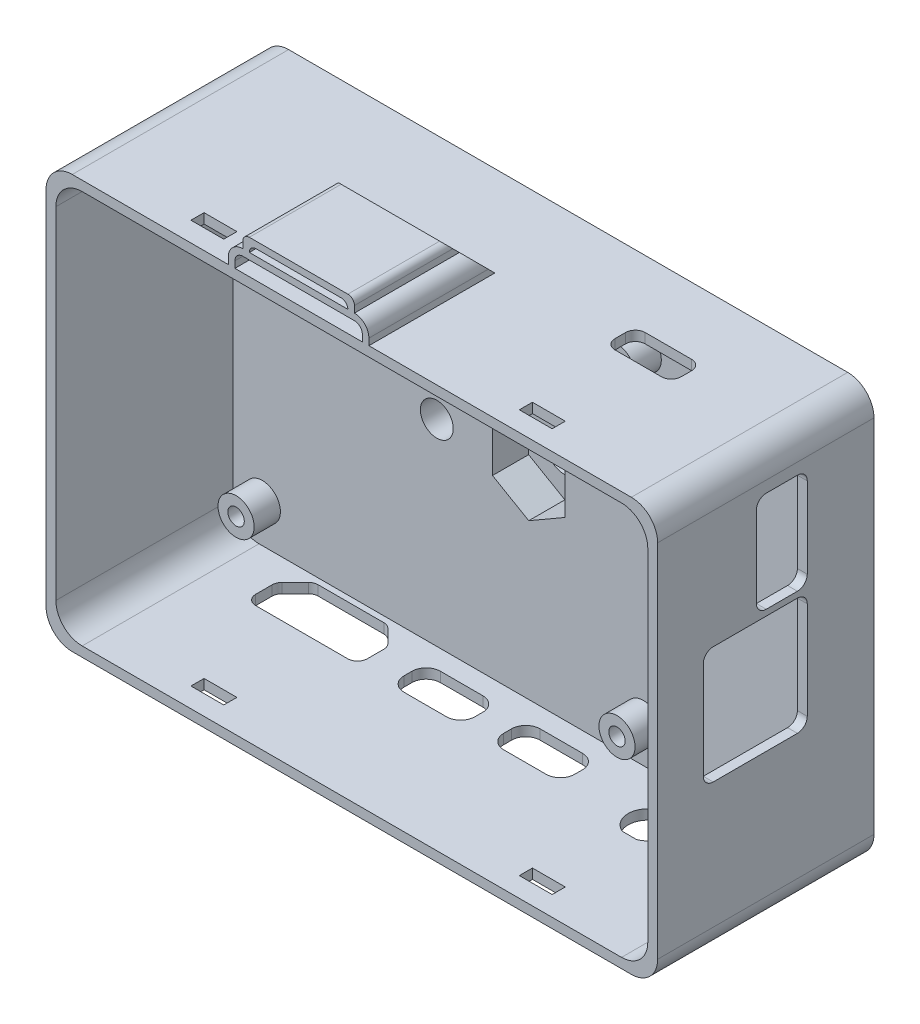
SolidWorks part; units mm, degrees
note: The reader was unsure of these and kept them because the rebuilt part matched: shared geometry of "Sketch1<3>", "Sketch8<2>".
ref_plane "Front Plane" through (0, 0, 0) normal (0, 0, 1) x (1, 0, 0)
ref_plane "Top Plane" through (0, 0, 0) normal (0, 1, 0) x (1, 0, 0)
ref_plane "Right Plane" through (0, 0, 0) normal (1, 0, 0) x (0, 0, -1)
sketch "Sketch1" plane through (0, 0, 0) normal (0, 0, 1) x (1, 0, 0)
  line L0 (46.565, -31.46) -> (46.565, 31.46)
  line L1 (45.065, -29.96) -> (-45.065, -29.96)
  line L2 (45.065, -29.96) -> (45.065, 29.96)
  line L3 (45.065, 29.96) -> (-45.065, 29.96)
  line L4 (-45.065, -29.96) -> (-45.065, 29.96)
  line L5 (45.065, -29.96) -> (-45.065, 29.96) construction
  line L6 (45.065, 29.96) -> (-45.065, -29.96) construction
  line L7 (46.565, 31.46) -> (-46.565, 31.46)
  line L8 (-46.565, -31.46) -> (-46.565, 31.46)
  line L9 (46.565, -31.46) -> (-46.565, -31.46)
  line L10 (44.065, 8.02) -> (44.065, -6.81) construction
  line L12 (21.895, 29.71) -> (28.965, 29.71) construction
  point P0 (0, 0)
  dimension "D2" = 1
  dimension "D3" = 0.25
  dimension "D1" = 1.5
extrude "Boss-Extrude1" add sketch "Sketch1" along normal blind 6 contours L2 L1 L4 L3
sketch "Sketch5" plane through (0, 0, 6) normal (0, 0, 1) x (1, 0, 0)
  circle A0 centre (17.435, -24.11) radius 1.4 construction
  circle A1 centre (-40.565, -24.11) radius 1.4 construction
  circle A2 centre (17.435, 24.89) radius 1.4 construction
  circle A3 centre (-40.565, 24.89) radius 1.4 construction
  circle A4 centre (17.435, -24.11) radius 1.4 construction
  circle A5 centre (-40.565, -24.11) radius 1.4 construction
  circle A6 centre (17.435, 24.89) radius 1.4 construction
  circle A7 centre (-40.565, 24.89) radius 1.4 construction
  circle A8 centre (17.435, 24.89) radius 1.25
  circle A9 centre (-40.565, 24.89) radius 1.25
  circle A10 centre (17.435, -24.11) radius 1.25
  circle A11 centre (-40.565, -24.11) radius 1.25
  circle A13 centre (-40.565, 24.89) radius 2.75
  circle A14 centre (17.435, 24.89) radius 2.75
  circle A15 centre (17.435, -24.11) radius 2.75
  circle A16 centre (-40.565, -24.11) radius 2.75
  dimension "D1" = 2.5
  dimension "D2" = 2.5
  dimension "D3" = 2.5
  dimension "D4" = 2.5
  dimension "D5" = 1.5
extrude "Boss-Extrude3" add sketch "Sketch5" along normal blind 4
extrude "Boss-Extrude2" add sketch "Sketch1<3>" along normal offset from surface (32.94 mm away) 6
sketch "Sketch1<3>" plane through (0, 0, 0) normal (0, 0, 1) x (1, 0, 0) same geometry as "Sketch1"
sketch "Sketch3" plane through (0, -31.46, 0) normal (0, -1, 0) x (1, 0, 0)
  line L31 (-19.165, 14.41) -> (-33.165, 14.41)
  line L32 (-34.665, 12.91) -> (-34.665, 10.4071)
  line L33 (-34.2257, 9.3464) -> (-32.2186, 7.3393)
  line L34 (-31.1579, 6.9) -> (-21.1721, 6.9)
  line L35 (-20.1114, 7.3393) -> (-18.1043, 9.3464)
  line L36 (-17.665, 10.4071) -> (-17.665, 12.91)
  line L37 (-19.165, 14.41) -> (-33.165, 14.41)
  line L38 (-34.665, 12.91) -> (-34.665, 10.4071)
  line L39 (-34.2257, 9.3464) -> (-32.2186, 7.3393)
  line L40 (-31.1579, 6.9) -> (-21.1721, 6.9)
  line L41 (-20.1114, 7.3393) -> (-18.1043, 9.3464)
  line L42 (-17.665, 10.4071) -> (-17.665, 12.91)
  line L45 (-10.455, 9) -> (-3.995, 9)
  line L46 (-1.825, 11.17) -> (-1.825, 12.37)
  line L47 (-3.995, 14.54) -> (-10.455, 14.54)
  line L48 (-12.625, 12.37) -> (-12.625, 11.17)
  line L49 (-10.455, 9) -> (-3.995, 9)
  line L50 (-1.825, 11.17) -> (-1.825, 12.37)
  line L51 (-3.995, 14.54) -> (-10.455, 14.54)
  line L52 (-12.625, 12.37) -> (-12.625, 11.17)
  line L57 (13.355, 11.17) -> (13.355, 12.37)
  line L58 (11.185, 14.54) -> (4.725, 14.54)
  line L59 (2.555, 12.37) -> (2.555, 11.17)
  line L60 (4.725, 9) -> (11.185, 9)
  line L61 (13.355, 11.17) -> (13.355, 12.37)
  line L62 (11.185, 14.54) -> (4.725, 14.54)
  line L63 (2.555, 12.37) -> (2.555, 11.17)
  line L64 (4.725, 9) -> (11.185, 9)
  line L65 (26.677, 16.26) -> (24.523, 16.26)
  line L66 (24.523, 10.66) -> (26.677, 10.66)
  line L67 (26.677, 16.26) -> (24.523, 16.26)
  line L68 (24.523, 10.66) -> (26.677, 10.66)
  line L83 (38.265, 10) -> (-41.265, 10) construction
  line L84 (37.1, 7) -> (23.1, 7)
  line L85 (37.6, 7.5) -> (37.6, 9.5)
  line L86 (37.1, 10) -> (23.1, 10)
  line L87 (22.6, 7.5) -> (22.6, 9.5)
  line L88 (37.6, 7) -> (22.6, 10) construction
  line L89 (37.6, 10) -> (22.6, 7) construction
  arc A25 (-17.665, 12.91) -> (-19.165, 14.41) centre (-19.165, 12.91) ccw
  arc A26 (-33.165, 14.41) -> (-34.665, 12.91) centre (-33.165, 12.91) ccw
  arc A27 (-34.665, 10.4071) -> (-34.2257, 9.3464) centre (-33.165, 10.4071) ccw
  arc A28 (-32.2186, 7.3393) -> (-31.1579, 6.9) centre (-31.1579, 8.4) ccw
  arc A29 (-21.1721, 6.9) -> (-20.1114, 7.3393) centre (-21.1721, 8.4) ccw
  arc A30 (-18.1043, 9.3464) -> (-17.665, 10.4071) centre (-19.165, 10.4071) ccw
  arc A31 (-17.665, 12.91) -> (-19.165, 14.41) centre (-19.165, 12.91) ccw
  arc A32 (-33.165, 14.41) -> (-34.665, 12.91) centre (-33.165, 12.91) ccw
  arc A33 (-34.665, 10.4071) -> (-34.2257, 9.3464) centre (-33.165, 10.4071) ccw
  arc A34 (-32.2186, 7.3393) -> (-31.1579, 6.9) centre (-31.1579, 8.4) ccw
  arc A35 (-21.1721, 6.9) -> (-20.1114, 7.3393) centre (-21.1721, 8.4) ccw
  arc A36 (-18.1043, 9.3464) -> (-17.665, 10.4071) centre (-19.165, 10.4071) ccw
  arc A39 (-12.625, 11.17) -> (-10.455, 9) centre (-10.455, 11.17) ccw
  arc A40 (-3.995, 9) -> (-1.825, 11.17) centre (-3.995, 11.17) ccw
  arc A41 (-1.825, 12.37) -> (-3.995, 14.54) centre (-3.995, 12.37) ccw
  arc A42 (-10.455, 14.54) -> (-12.625, 12.37) centre (-10.455, 12.37) ccw
  arc A43 (-12.625, 11.17) -> (-10.455, 9) centre (-10.455, 11.17) ccw
  arc A44 (-3.995, 9) -> (-1.825, 11.17) centre (-3.995, 11.17) ccw
  arc A45 (-1.825, 12.37) -> (-3.995, 14.54) centre (-3.995, 12.37) ccw
  arc A46 (-10.455, 14.54) -> (-12.625, 12.37) centre (-10.455, 12.37) ccw
  arc A51 (11.185, 9) -> (13.355, 11.17) centre (11.185, 11.17) ccw
  arc A52 (13.355, 12.37) -> (11.185, 14.54) centre (11.185, 12.37) ccw
  arc A53 (4.725, 14.54) -> (2.555, 12.37) centre (4.725, 12.37) ccw
  arc A54 (2.555, 11.17) -> (4.725, 9) centre (4.725, 11.17) ccw
  arc A55 (11.185, 9) -> (13.355, 11.17) centre (11.185, 11.17) ccw
  arc A56 (13.355, 12.37) -> (11.185, 14.54) centre (11.185, 12.37) ccw
  arc A57 (4.725, 14.54) -> (2.555, 12.37) centre (4.725, 12.37) ccw
  arc A58 (2.555, 11.17) -> (4.725, 9) centre (4.725, 11.17) ccw
  arc A59 (26.677, 10.66) -> (26.677, 16.26) centre (25.6, 13.46) ccw
  arc A60 (24.523, 16.26) -> (24.523, 10.66) centre (25.6, 13.46) ccw
  arc A61 (26.677, 10.66) -> (26.677, 16.26) centre (25.6, 13.46) ccw
  arc A62 (24.523, 16.26) -> (24.523, 10.66) centre (25.6, 13.46) ccw
  arc A77 (23.1, 7) -> (22.6, 7.5) centre (23.1, 7.5) cw
  arc A78 (37.1, 7) -> (37.6, 7.5) centre (37.1, 7.5) ccw
  arc A79 (37.6, 9.5) -> (37.1, 10) centre (37.1, 9.5) ccw
  arc A80 (23.1, 10) -> (22.6, 9.5) centre (23.1, 9.5) ccw
  point P0 (30.1, 8.5)
  point P7 (22.6, 13.46)
  dimension "D9" = 0.5
  dimension "D5" = 3
  dimension "D6" = 15
  dimension "D7" = 0
  dimension "D1" = 1
  dimension "D2" = 1
  dimension "D3" = 1
  dimension "D4" = 0.5
extrude "Cut-Extrude1" cut sketch "Sketch3" against normal up to next
sketch "Sketch4" plane through (0, 31.46, 0) normal (0, 1, 0) x (1, 0, 0)
  line L8 (21.895, -14.76) -> (28.965, -14.76)
  line L9 (30.465, -13.26) -> (30.465, -11.66)
  line L10 (28.965, -10.16) -> (21.895, -10.16)
  line L11 (20.395, -11.66) -> (20.395, -13.26)
  line L12 (21.895, -14.76) -> (28.965, -14.76)
  line L13 (30.465, -13.26) -> (30.465, -11.66)
  line L14 (28.965, -10.16) -> (21.895, -10.16)
  line L15 (20.395, -11.66) -> (20.395, -13.26)
  arc A8 (20.395, -13.26) -> (21.895, -14.76) centre (21.895, -13.26) ccw
  arc A9 (28.965, -14.76) -> (30.465, -13.26) centre (28.965, -13.26) ccw
  arc A10 (30.465, -11.66) -> (28.965, -10.16) centre (28.965, -11.66) ccw
  arc A11 (21.895, -10.16) -> (20.395, -11.66) centre (21.895, -11.66) ccw
  arc A12 (20.395, -13.26) -> (21.895, -14.76) centre (21.895, -13.26) ccw
  arc A13 (28.965, -14.76) -> (30.465, -13.26) centre (28.965, -13.26) ccw
  arc A14 (30.465, -11.66) -> (28.965, -10.16) centre (28.965, -11.66) ccw
  arc A15 (21.895, -10.16) -> (20.395, -11.66) centre (21.895, -11.66) ccw
  dimension "D1" = 1
extrude "Cut-Extrude3" cut sketch "Sketch4" against normal up to next
fillet "Fillet1" radius 4 8 edges at (46.565, 31.46, 16.47) (45.065, 29.96, 19.47) (45.065, -29.96, 19.47) (46.565, -31.46, 16.47) (-46.565, -31.46, 16.47) (-46.565, 31.46, 16.47) (-45.065, 29.96, 19.47) (-45.065, -29.96, 19.47)
sketch "Sketch6" plane through (46.565, 0, 0) normal (1, 0, 0) x (0, 0, -1)
  line L8 (-11.66, 9.52) -> (-24.49, 9.52)
  line L9 (-25.99, 8.02) -> (-25.99, -6.81)
  line L10 (-24.49, -8.31) -> (-11.66, -8.31)
  line L11 (-10.16, -6.81) -> (-10.16, 8.02)
  line L12 (-11.66, 9.52) -> (-24.49, 9.52)
  line L13 (-25.99, 8.02) -> (-25.99, -6.81)
  line L14 (-24.49, -8.31) -> (-11.66, -8.31)
  line L15 (-10.16, -6.81) -> (-10.16, 8.02)
  line L20 (-11.66, 25.73) -> (-16.41, 25.73)
  line L21 (-17.91, 24.23) -> (-17.91, 11.93)
  line L22 (-16.41, 10.43) -> (-11.66, 10.43)
  line L23 (-10.16, 11.93) -> (-10.16, 24.23)
  line L24 (-11.66, 25.73) -> (-16.41, 25.73)
  line L25 (-17.91, 24.23) -> (-17.91, 11.93)
  line L26 (-16.41, 10.43) -> (-11.66, 10.43)
  line L27 (-10.16, 11.93) -> (-10.16, 24.23)
  arc A8 (-10.16, 8.02) -> (-11.66, 9.52) centre (-11.66, 8.02) ccw
  arc A9 (-24.49, 9.52) -> (-25.99, 8.02) centre (-24.49, 8.02) ccw
  arc A10 (-25.99, -6.81) -> (-24.49, -8.31) centre (-24.49, -6.81) ccw
  arc A11 (-11.66, -8.31) -> (-10.16, -6.81) centre (-11.66, -6.81) ccw
  arc A12 (-10.16, 8.02) -> (-11.66, 9.52) centre (-11.66, 8.02) ccw
  arc A13 (-24.49, 9.52) -> (-25.99, 8.02) centre (-24.49, 8.02) ccw
  arc A14 (-25.99, -6.81) -> (-24.49, -8.31) centre (-24.49, -6.81) ccw
  arc A15 (-11.66, -8.31) -> (-10.16, -6.81) centre (-11.66, -6.81) ccw
  arc A20 (-10.16, 24.23) -> (-11.66, 25.73) centre (-11.66, 24.23) ccw
  arc A21 (-16.41, 25.73) -> (-17.91, 24.23) centre (-16.41, 24.23) ccw
  arc A22 (-17.91, 11.93) -> (-16.41, 10.43) centre (-16.41, 11.93) ccw
  arc A23 (-11.66, 10.43) -> (-10.16, 11.93) centre (-11.66, 11.93) ccw
  arc A24 (-10.16, 24.23) -> (-11.66, 25.73) centre (-11.66, 24.23) ccw
  arc A25 (-16.41, 25.73) -> (-17.91, 24.23) centre (-16.41, 24.23) ccw
  arc A26 (-17.91, 11.93) -> (-16.41, 10.43) centre (-16.41, 11.93) ccw
  arc A27 (-11.66, 10.43) -> (-10.16, 11.93) centre (-11.66, 11.93) ccw
  dimension "D1" = 1
  dimension "D2" = 1
extrude "Cut-Extrude5" cut sketch "Sketch6" against normal up to next
sketch "Sketch7" plane through (0, 0, 0) normal (0, 0, -1) x (-1, 0, 0)
  line L0 (18.805, 31.46) -> (18.805, 32.46)
  line L1 (15.605, 34.66) -> (0.605, 34.66)
  line L2 (-2.595, 32.46) -> (-2.595, 31.46)
  line L14 (-2.595, 31.46) -> (-1.595, 31.46)
  line L16 (17.805, 31.46) -> (18.805, 31.46)
  line L17 (-0.395, 33.46) -> (16.605, 33.46) construction
  line L18 (-1.395, 32.46) -> (-1.395, 31.46) construction
  line L19 (17.605, 31.46) -> (17.605, 32.46) construction
  line L20 (-42.565, 31.46) -> (42.565, 31.46) construction
  line L54 (17.805, 31.46) -> (17.805, 32.46)
  line L55 (16.605, 33.66) -> (-0.395, 33.66)
  line L56 (-1.595, 32.46) -> (-1.595, 31.46)
  line L62 (16.605, 34.66) -> (-0.395, 34.66) construction
  line L63 (0.605, 34.66) -> (15.605, 34.66)
  line L64 (-0.395, 34.66) -> (-0.395, 36.66)
  line L65 (-0.395, 36.66) -> (16.605, 36.66)
  line L66 (16.605, 34.66) -> (16.605, 36.66)
  line L67 (0.605, 34.66) -> (15.605, 34.66)
  line L68 (0.605, 34.66) -> (0.605, 35.66)
  line L69 (0.605, 35.66) -> (15.605, 35.66)
  line L70 (15.605, 34.66) -> (15.605, 35.66)
  arc A0 (18.805, 32.46) -> (16.605, 34.66) centre (16.605, 32.46) ccw
  arc A1 (-0.395, 34.66) -> (-2.595, 32.46) centre (-0.395, 32.46) ccw
  arc A2 (-0.395, 33.46) -> (-1.395, 32.46) centre (-0.395, 32.46) ccw construction
  arc A3 (17.605, 32.46) -> (16.605, 33.46) centre (16.605, 32.46) ccw construction
  arc A14 (17.805, 32.46) -> (16.605, 33.66) centre (16.605, 32.46) ccw
  arc A15 (-0.395, 33.66) -> (-1.595, 32.46) centre (-0.395, 32.46) ccw
  line M9 (42.565, 31.46) -> (-42.565, 31.46)
  dimension "D7" = 0.2
  dimension "D9" = 0.2
  dimension "D2" = 1
  dimension "D3" = 2
  dimension "D4" = 1
  dimension "D5" = 1
  dimension "D6" = 1
  dimension "D1" = 0.2
  dimension "D8" = 0.2
  dimension "D10" = 0.2
extrude "Boss-Extrude4" add sketch "Sketch7" along normal up to surface (19.18 mm away) from surface contours A0 L62 L1 A1 L2 L56 A15 L55 A14 L54 L0 M9 | L62 L66 L65 L64 L68 L69 L70
sketch "Sketch8" plane through (0, 0, 0) normal (0, 1, 0) x (1, 0, 0)
  line L0 (25, -28.94) -> (-25, -28.94) construction
  line L1 (-42.565, -32.94) -> (42.565, -32.94) construction
  line L3 (-22.5, -27.94) -> (-27.5, -27.94)
  line L4 (-22.5, -27.94) -> (-22.5, -29.94)
  line L5 (-22.5, -29.94) -> (-27.5, -29.94)
  line L6 (-27.5, -27.94) -> (-27.5, -29.94)
  line L7 (-22.5, -27.94) -> (-27.5, -29.94) construction
  line L8 (-22.5, -29.94) -> (-27.5, -27.94) construction
  line L9 (27.5, -27.94) -> (22.5, -27.94)
  line L10 (27.5, -27.94) -> (27.5, -29.94)
  line L11 (27.5, -29.94) -> (22.5, -29.94)
  line L12 (22.5, -27.94) -> (22.5, -29.94)
  line L13 (27.5, -27.94) -> (22.5, -29.94) construction
  line L14 (27.5, -29.94) -> (22.5, -27.94) construction
  point P3 (0, -28.94)
  point P5 (0, -32.94)
  dimension "D1" = 4
  dimension "D2" = 5
  dimension "D3" = 2
  dimension "D4" = 5
  dimension "D5" = 2
  dimension "D6" = 50
extrude "Cut-Extrude6" cut sketch "Sketch8" against normal up to next from surface
extrude "Cut-Extrude7" cut sketch "Sketch8<2>" along normal up to next from surface
sketch "Sketch8<2>" plane through (0, 0, 0) normal (0, 1, 0) x (1, 0, 0) same geometry as "Sketch8"
fillet "Fillet2" radius 1 4 edges at (0.395, 36.66, 23.35) (-16.605, 36.66, 23.35) (-15.605, 35.66, 23.35) (-0.605, 35.66, 23.35)
sketch "Sketch10" plane through (-18.805, 0, 0) normal (-1, 0, 0) x (0, 0, 1)
  line L5 (13.76, 36.66) -> (18.96, 36.66)
  line L6 (13.76, 36.66) -> (32.94, 36.66) construction
  line L7 (18.96, 36.66) -> (13.76, 31.46)
  line L8 (13.76, 31.46) -> (13.76, 36.66)
  dimension "D1" = 45
extrude "Cut-Extrude8" cut sketch "Sketch10" against normal up to surface (21.4 mm away) up to face at (2.595, 31.96, 23.35)
sketch "Sketch11" plane through (0, 0, 6) normal (0, 0, -1) x (-1, 0, 0)
  line L1 (0, 6.3797) -> (-5.525, 3.1899)
  line L2 (-5.525, 3.1899) -> (-5.525, -3.1899)
  line L3 (-5.525, -3.1899) -> (0, -6.3797)
  line L4 (0, -6.3797) -> (5.525, -3.1899)
  line L5 (5.525, -3.1899) -> (5.525, 3.1899)
  line L6 (5.525, 3.1899) -> (0, 6.3797)
  circle A0 centre (0, 0) radius 5.525 construction
  dimension "D1" = 11.05
extrude "Cut-Extrude9" cut sketch "Sketch11" along normal blind 5.5
sketch "Sketch12" plane through (0, 0, 6) normal (0, 0, 1) x (1, 0, 0)
  circle A0 centre (0, 0) radius 3.075
  circle A1 centre (-14, 0) radius 2.5
  dimension "D1" = 6.15
  dimension "D2" = 5
  dimension "D3" = 14
extrude "Cut-Extrude10" cut sketch "Sketch12" against normal up to next
